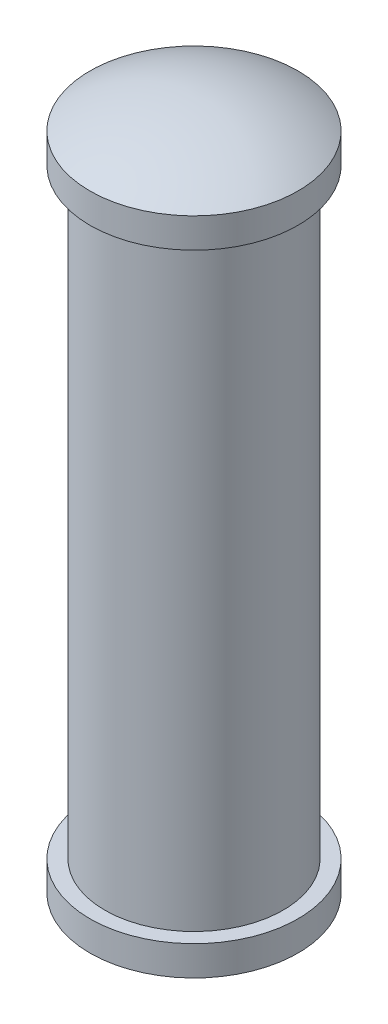
SolidWorks part; units mm, degrees
ref_plane "Plano frontal" through (0, 0, 0) normal (0, 0, 1) x (1, 0, 0)
ref_plane "Plano superior" through (0, 0, 0) normal (0, 1, 0) x (1, 0, 0)
ref_plane "Plano direito" through (0, 0, 0) normal (1, 0, 0) x (0, 0, -1)
sketch "Sketch1" plane through (0, 0, 0) normal (0, 0, 1) x (1, 0, 0)
  line L0 (0, 5.9508) -> (0, -6.1148) construction
  line L1 (-7.276, 0) -> (7.7404, 0) construction
  line L2 (0, 0) -> (-3, 0)
  line L3 (0, 0) -> (0, 10.1)
  line L4 (-3, 0) -> (-3, 10.1)
  line L5 (0, 10.1) -> (-3, 10.1)
  dimension "D1" = 10.1
  dimension "D2" = 3
revolve "Revolve1" add sketch "Sketch1" angle 360 about L0
sketch "Sketch2" plane through (0, 10.1, 0) normal (0, 1, 0) x (1, 0, 0)
  circle A0 centre (0, 0) radius 3.5
  dimension "D1" = 7
extrude "Boss-Extrude1" add sketch "Sketch2" along normal blind 1
dome "Dome1" faces to dome 1 distance 1 reverse direction no elliptical dome no face at (0, 11.1, 3.5) parameters "D1"=1
mirror "Mirror1" about plane through (0, 0, 0) normal (0, 1, 0) of "Revolve1", "Boss-Extrude1", "Dome1"
